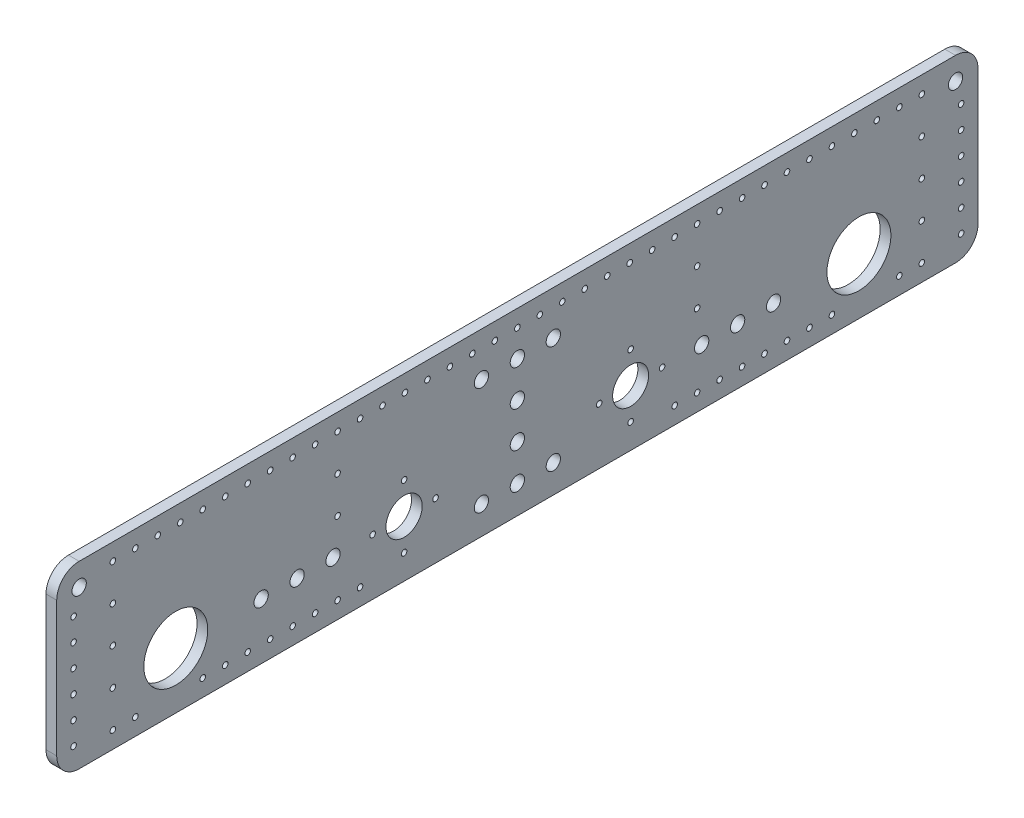
SolidWorks part; units mm, degrees
ref_plane "Front Plane" through (0, 0, 0) normal (0, 0, 1) x (1, 0, 0)
ref_plane "Top Plane" through (0, 0, 0) normal (0, 1, 0) x (1, 0, 0)
ref_plane "Right Plane" through (0, 0, 0) normal (1, 0, 0) x (0, 0, -1)
sketch "Sketch2" plane through (0, 0, 0) normal (1, 0, 0) x (0, 0, -1)
  line L0 (-23.4723, 28.6683) -> (-23.4723, -31.3317)
  line L1 (-13.4723, 38.6683) -> (376.5277, 38.6683)
  line L2 (-13.4723, -41.3317) -> (376.5277, -41.3317)
  line L3 (386.5277, 28.6683) -> (386.5277, -31.3317)
  circle A1 centre (29.5277, -16.3317) radius 14.225
  circle A2 centre (333.5277, -16.3317) radius 14.225
  arc A15 (-23.4723, 28.6683) -> (-13.4723, 38.6683) centre (-13.4723, 28.6683) cw
  arc A16 (-13.4723, -41.3317) -> (-23.4723, -31.3317) centre (-13.4723, -31.3317) cw
  arc A17 (386.5277, 28.6683) -> (376.5277, 38.6683) centre (376.5277, 28.6683) ccw
  arc A18 (376.5277, -41.3317) -> (386.5277, -31.3317) centre (376.5277, -31.3317) ccw
  circle A59 centre (181.5277, -28.7717) radius 3.18
  circle A60 centre (197.5277, -28.7717) radius 3.18
  circle A63 centre (197.5277, 19.2283) radius 3.18
  circle A64 centre (181.5277, -12.7717) radius 3.18
  circle A65 centre (181.5277, 3.2283) radius 3.18
  circle A66 centre (181.5277, 19.2283) radius 3.18
  circle A67 centre (165.5277, -28.7717) radius 3.18
  circle A68 centre (165.5277, 19.2283) radius 3.18
  circle A69 centre (197.5277, -12.7717) radius 3.18 [skipped]
  circle A70 centre (197.5277, 3.2283) radius 3.18 [skipped]
  circle A71 centre (-8.4723, 31.1683) radius 1.25 construction
  circle A150 centre (83.5027, -16.3317) radius 3.18
  circle A151 centre (279.5527, -16.3317) radius 3.18
  circle A152 centre (1.5277, 31.1683) radius 1.25
  circle A153 centre (11.5277, 31.1683) radius 1.25
  circle A154 centre (21.5277, 31.1683) radius 1.25
  circle A155 centre (31.5277, 31.1683) radius 1.25
  circle A156 centre (41.5277, 31.1683) radius 1.25
  circle A157 centre (51.5277, 31.1683) radius 1.25
  circle A158 centre (61.5277, 31.1683) radius 1.25
  circle A159 centre (71.5277, 31.1683) radius 1.25
  circle A160 centre (81.5277, 31.1683) radius 1.25
  circle A161 centre (91.5277, 31.1683) radius 1.25
  circle A162 centre (101.5277, 31.1683) radius 1.25
  circle A163 centre (111.5277, 31.1683) radius 1.25
  circle A164 centre (121.5277, 31.1683) radius 1.25
  circle A165 centre (131.5277, 31.1683) radius 1.25
  circle A166 centre (141.5277, 31.1683) radius 1.25
  circle A167 centre (151.5277, 31.1683) radius 1.25
  circle A168 centre (161.5277, 31.1683) radius 1.25
  circle A169 centre (171.5277, 31.1683) radius 1.25
  circle A170 centre (181.5277, 31.1683) radius 1.25
  circle A171 centre (191.5277, 31.1683) radius 1.25
  circle A172 centre (201.5277, 31.1683) radius 1.25
  circle A173 centre (211.5277, 31.1683) radius 1.25
  circle A174 centre (221.5277, 31.1683) radius 1.25
  circle A175 centre (231.5277, 31.1683) radius 1.25
  circle A176 centre (241.5277, 31.1683) radius 1.25
  circle A177 centre (251.5277, 31.1683) radius 1.25
  circle A178 centre (261.5277, 31.1683) radius 1.25
  circle A179 centre (271.5277, 31.1683) radius 1.25
  circle A180 centre (281.5277, 31.1683) radius 1.25
  circle A181 centre (291.5277, 31.1683) radius 1.25
  circle A182 centre (301.5277, 31.1683) radius 1.25
  circle A183 centre (311.5277, 31.1683) radius 1.25
  circle A184 centre (321.5277, 31.1683) radius 1.25
  circle A185 centre (331.5277, 31.1683) radius 1.25
  circle A186 centre (341.5277, 31.1683) radius 1.25
  circle A187 centre (351.5277, 31.1683) radius 1.25
  circle A188 centre (361.5277, 31.1683) radius 1.25
  circle A190 centre (1.5277, -33.8317) radius 1.25
  circle A191 centre (11.5277, -33.8317) radius 1.25
  circle A194 centre (41.5277, -33.8317) radius 1.25
  circle A195 centre (51.5277, -33.8317) radius 1.25
  circle A196 centre (61.5277, -33.8317) radius 1.25
  circle A197 centre (71.5277, -33.8317) radius 1.25
  circle A198 centre (81.5277, -33.8317) radius 1.25
  circle A199 centre (91.5277, -33.8317) radius 1.25
  circle A200 centre (101.5277, -33.8317) radius 1.25
  circle A201 centre (111.5277, -33.8317) radius 1.25
  circle A215 centre (251.5277, -33.8317) radius 1.25
  circle A216 centre (261.5277, -33.8317) radius 1.25
  circle A217 centre (271.5277, -33.8317) radius 1.25
  circle A218 centre (281.5277, -33.8317) radius 1.25
  circle A219 centre (291.5277, -33.8317) radius 1.25
  circle A220 centre (301.5277, -33.8317) radius 1.25
  circle A221 centre (311.5277, -33.8317) radius 1.25
  circle A222 centre (321.5277, -33.8317) radius 1.25
  circle A225 centre (351.5277, -33.8317) radius 1.25
  circle A226 centre (361.5277, -33.8317) radius 1.25
  circle A229 centre (181.5277, -33.8317) radius 1.25 [skipped]
  circle A230 centre (201.5277, -33.8317) radius 1.25 [skipped]
  circle A231 centre (161.5277, -33.8317) radius 1.25 [skipped]
  circle A232 centre (151.5277, -33.8317) radius 1.25 [skipped]
  circle A233 centre (141.5277, -33.8317) radius 1.25 [skipped]
  circle A234 centre (131.5277, -33.8317) radius 1.25 [skipped]
  circle A235 centre (171.5277, -33.8317) radius 1.25 [skipped]
  circle A236 centre (191.5277, -33.8317) radius 1.25 [skipped]
  circle A237 centre (211.5277, -33.8317) radius 1.25 [skipped]
  circle A238 centre (221.5277, -33.8317) radius 1.25 [skipped]
  circle A239 centre (231.5277, -33.8317) radius 1.25 [skipped]
  circle A240 centre (31.5277, -33.8317) radius 1.25 [skipped]
  circle A241 centre (21.5277, -33.8317) radius 1.25 [skipped]
  circle A242 centre (331.5277, -33.8317) radius 1.25 [skipped]
  circle A243 centre (341.5277, -33.8317) radius 1.25 [skipped]
  circle A245 centre (-13.4723, 28.6683) radius 3.18
  circle A247 centre (376.5277, 28.6683) radius 3.18
  circle A248 centre (371.5277, 31.1683) radius 1.25 [skipped]
  circle A249 centre (371.5277, -33.8317) radius 1.25 [skipped]
  circle A250 centre (-8.4723, -33.8317) radius 1.25 [skipped]
  circle A254 centre (295.5527, -16.3317) radius 3.18
  circle A255 centre (67.5027, -16.3317) radius 3.18
  circle A256 centre (263.5527, -16.3317) radius 3.18
  circle A257 centre (121.5277, -33.8317) radius 1.25 [skipped]
  circle A260 centre (131.1277, -30.3317) radius 1.25
  circle A261 centre (145.1277, -16.3317) radius 1.25
  circle A262 centre (131.1277, -2.3317) radius 1.25
  circle A263 centre (117.1277, -16.3317) radius 1.25
  circle A264 centre (231.9277, -30.3317) radius 1.25
  circle A265 centre (217.9277, -16.3317) radius 1.25
  circle A266 centre (231.9277, -2.3317) radius 1.25
  circle A267 centre (245.9277, -16.3317) radius 1.25
  circle A268 centre (231.9277, -16.3317) radius 8
  circle A269 centre (131.1277, -16.3317) radius 8.0683
  circle A270 centre (241.5277, -33.8317) radius 1.25 [skipped]
  circle A271 centre (-15.9723, 18.6683) radius 1.25
  circle A272 centre (379.0277, 18.6683) radius 1.25
  circle A273 centre (379.0277, 8.6683) radius 1.25
  circle A274 centre (379.0277, -1.3317) radius 1.25
  circle A275 centre (379.0277, -11.3317) radius 1.25
  circle A276 centre (379.0277, -21.3317) radius 1.25
  circle A277 centre (379.0277, -31.3317) radius 1.25
  circle A278 centre (-15.9723, 8.6683) radius 1.25
  circle A279 centre (-15.9723, -1.3317) radius 1.25
  circle A280 centre (-15.9723, -11.3317) radius 1.25
  circle A281 centre (-15.9723, -21.3317) radius 1.25
  circle A282 centre (-15.9723, -31.3317) radius 1.25
  circle A284 centre (101.5277, -1.3317) radius 1.25
  circle A285 centre (101.5277, 14.9183) radius 1.25
  arc A286 (101.4697, -18.8304) -> (102.6179, -16.9702) centre (99.5027, -16.3317) ccw [skipped]
  circle A287 centre (361.5277, -17.5817) radius 1.25
  circle A288 centre (361.5277, -1.3317) radius 1.25
  circle A289 centre (361.5277, 14.9183) radius 1.25
  circle A290 centre (1.5277, -17.5817) radius 1.25
  circle A291 centre (1.5277, -1.3317) radius 1.25
  circle A292 centre (1.5277, 14.9183) radius 1.25
  circle A293 centre (101.5277, -17.5817) radius 1.25 [skipped]
  circle A294 centre (99.5027, -16.3317) radius 3.18
  circle A298 centre (261.5277, -1.3317) radius 1.25
  circle A300 centre (261.5277, 14.9183) radius 1.25
  arc A301 (260.4374, -16.9702) -> (261.5857, -18.8304) centre (261.5277, -17.5817) ccw [skipped]
  arc A302 (80.4021, 31.712) -> (81.5373, 29.9183) centre (83.5027, 32.4183) ccw [skipped]
  circle A303 centre (83.5027, 16.1683) radius 3.18 [skipped]
  circle A304 centre (83.5027, -0.0817) radius 3.18 [skipped]
  point P32 (-23.4723, 38.6683)
  point P35 (-23.4723, -41.3317)
  point P40 (386.5277, -41.3317)
  point P123 (181.5277, -41.3317)
  dimension "D3" = 25
  dimension "D7" = 10
  dimension "D8" = 10
  dimension "D9" = 10
  dimension "D10" = 10
  dimension "D11" = 7.5
  dimension "D13" = 12.56
  dimension "D20" = 7.5
  dimension "D1" = 80
  dimension "D2" = 410
  dimension "D4" = 53
  dimension "D5" = 25
  dimension "D6" = 53
  dimension "D12" = 15
  dimension "D14" = 205
  dimension "D21" = 20
  dimension "D15" = 2
  dimension "D16" = 4
  dimension "D17" = 2
  dimension "D18" = 39
  dimension "D19" = 2
  dimension "D22" = 2
  dimension "D23" = 2
  dimension "D24" = 2
  dimension "D25" = 6
  dimension "D26" = 4
  dimension "D27" = 4
  dimension "D28" = 4
  dimension "D29" = 2
  dimension "D30" = 4
extrude "Boss-Extrude1" add sketch "Sketch2" along normal blind 4.7625
